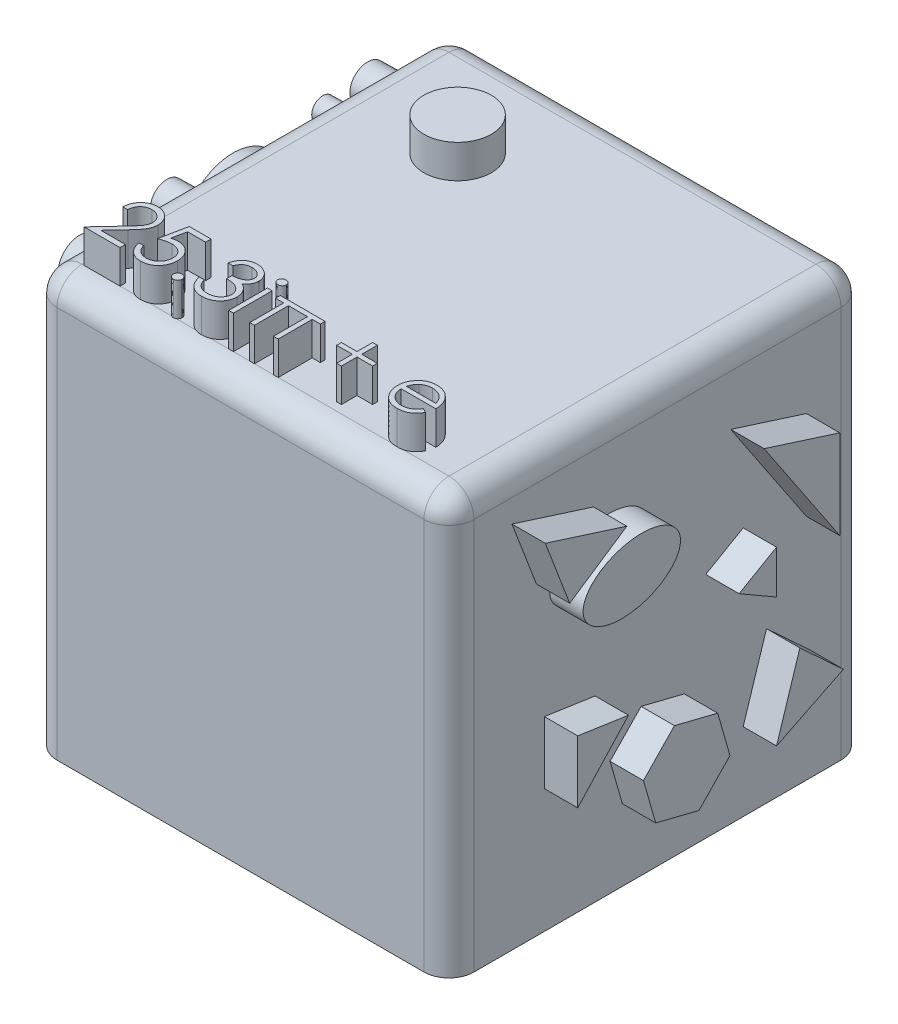
SolidWorks part; units mm, degrees
ref_plane "Front Plane" through (0, 0, 0) normal (0, 0, 1) x (1, 0, 0)
ref_plane "Top Plane" through (0, 0, 0) normal (0, 1, 0) x (1, 0, 0)
ref_plane "Right Plane" through (0, 0, 0) normal (1, 0, 0) x (0, 0, -1)
sketch "Sketch1" plane through (0, 0, 0) normal (0, 1, 0) x (1, 0, 0)
  line L1 (0, 0) -> (25, 0)
  line L2 (0, 0) -> (0, -25)
  line L3 (0, -25) -> (25, -25)
  line L4 (25, 0) -> (25, -25)
extrude "Boss-Extrude1" add sketch "Sketch1" along normal blind 25
fillet "Fillet1" radius 1.5 8 edges at (0, 12.5, 25) (0, 12.5, 0) (25, 12.5, 0) (25, 12.5, 25) (0, 25, 12.5) (12.5, 25, 0) (12.5, 25, 25) (25, 25, 12.5)
sketch "Sketch6" plane through (0, 25, 0) normal (0, 1, 0) x (1, 0, 0)
  circle A0 centre (6.997, -6.4811) radius 2.0261
  point P2 (0, 0)
extrude "Boss-Extrude5" add sketch "Sketch6" along normal blind 2
sketch "Sketch7" plane through (0, 0, 0) normal (0, -1, 0) x (-1, 0, 0)
  circle A0 centre (-5.9652, -19.1208) radius 3.5955
  circle A1 centre (-15.8104, -15.0795) radius 0.7155
  circle A2 centre (-16.5259, -19.5508) radius 2.0598
  circle A3 centre (-7.9428, -9.3616) radius 1.5861
  circle A4 centre (-17.1432, -9.7485) radius 2.3972
  circle A5 centre (-11.7691, -4.8903) radius 3.6277
extrude "Boss-Extrude6" add sketch "Sketch7" along normal blind 2
sketch "Sketch8" plane through (0, 0, 0) normal (-1, 0, 0) x (0, 0, 1)
  circle A0 centre (5.5679, 18.5843) radius 1.7646
  circle A1 centre (10.954, 19.6814) radius 3.1065
  circle A2 centre (7.8475, 13.647) radius 0.5476
  circle A3 centre (14.0605, 14.6943) radius 1.2507
  circle A4 centre (17.6367, 19.1329) radius 1.052
  circle A5 centre (10.1561, 9.6573) radius 0.4516
  circle A6 centre (3.8033, 11.0537) radius 1.6179
  circle A7 centre (7.3, 11.4028) radius 1.0224
  circle A8 centre (15.3112, 10.1089) radius 0.7751
  circle A9 centre (10.6077, 13.0995) radius 1.2373
  circle A10 centre (17.2378, 13.4436) radius 1.5191
  circle A11 centre (5.8671, 7.1638) radius 1.2175
  circle A12 centre (10.6077, 6.7149) radius 1.3695
  circle A13 centre (15.7416, 7.1638) radius 0.83
  circle A14 centre (3.8033, 2.8749) radius 1.88
  circle A15 centre (9.2381, 2.8749) radius 1.5372
  circle A16 centre (14.9116, 3.6728) radius 1.1514
  circle A17 centre (19.2326, 4.8242) radius 1.46
  circle A18 centre (19.7313, 10.1089) radius 1.7901
  circle A19 centre (20.1303, 16.9884) radius 1.3866
  circle A20 centre (20.1303, 21.776) radius 1.3419
  circle A21 centre (14.9116, 22.3745) radius 1.0233
  circle A22 centre (2.8749, 15.5421) radius 1.2468
  circle A23 centre (2.8749, 22.3745) radius 1.1046
  circle A24 centre (6.2661, 16.0907) radius 0.5576
  circle A25 centre (4.77, 14.2954) radius 0.2686
  circle A26 centre (9.2381, 16.0907) radius 0.6904
  circle A27 centre (2.3263, 7.862) radius 0.8879
  circle A28 centre (17.2378, 2.3263) radius 1.0673
  circle A29 centre (20.1303, 2.3263) radius 0.5985
  circle A30 centre (21.1277, 7.1638) radius 0.83
  circle A31 centre (12.3005, 10.6548) radius 1.3091
  circle A32 centre (5.5679, 22.3745) radius 0.6982
  circle A33 centre (2.3263, 19.1329) radius 0.7758
  circle A34 centre (21.1277, 13.4436) radius 0.8977
  circle A35 centre (15.7416, 16.9884) radius 0.9836
  circle A36 centre (14.9116, 19.9087) radius 0.4597
  circle A37 centre (13.2979, 7.1638) radius 0.8848
  circle A38 centre (12.3005, 1.9273) radius 0.8118
extrude "Boss-Extrude8" add sketch "Sketch8" along normal blind 2 draft 1
sketch "Sketch9" plane through (25, 0, 0) normal (1, 0, 0) x (0, 0, -1)
  line L1 (-10.1561, 5.5679) -> (-10.8912, 8.1379)
  line L2 (-10.8912, 8.1379) -> (-13.4845, 8.7863)
  line L3 (-13.4845, 8.7863) -> (-15.3427, 6.8646)
  line L4 (-15.3427, 6.8646) -> (-14.6075, 4.2945)
  line L5 (-14.6075, 4.2945) -> (-12.0142, 3.6462)
  line L6 (-12.0142, 3.6462) -> (-10.1561, 5.5679)
  circle A0 centre (-12.7494, 6.2162) radius 2.315 construction
  ellipse E0 centre (-16.0409, 17.8362) end of major axis (-18.9334, 17.1879) minor radius 1.8526
extrude "Boss-Extrude9" add sketch "Sketch9" along normal blind 2
sketch "Sketch10" plane through (25, 0, 0) normal (1, 0, 0) x (0, 0, -1)
  line L0 (-19.2825, 7.4131) -> (-19.2825, 11.1535)
  line L1 (-9.6075, 13.6969) -> (-7.3633, 12.4012)
  line L2 (-7.3633, 12.4012) -> (-7.3633, 14.9926)
  line L3 (-7.3633, 14.9926) -> (-9.6075, 13.6969)
  line L4 (-19.2825, 11.1535) -> (-16.2403, 10.7046)
  line L5 (-16.2403, 10.7046) -> (-19.2825, 7.4131)
  line L6 (-8.1113, 20.4794) -> (-3.5731, 19.0331)
  line L7 (-3.5731, 19.0331) -> (-3.5731, 13.6969)
  line L8 (-3.5731, 13.6969) -> (-8.1113, 20.4794)
  line L9 (-7.3633, 4.6702) -> (-5.9647, 9.0589)
  line L10 (-5.9647, 9.0589) -> (-3.3553, 6.6472)
  line L11 (-3.3553, 6.6472) -> (-7.3633, 4.6702)
  line L12 (-21.2275, 22.1251) -> (-16.3394, 20.5674)
  line L13 (-16.3394, 20.5674) -> (-19.7613, 18.2777)
  line L14 (-19.7613, 18.2777) -> (-21.2275, 22.1251)
  circle A0 centre (-8.1113, 13.6969) radius 0.7481 construction
extrude "Boss-Extrude10" add sketch "Sketch10" along normal blind 2
sketch "Sketch11" plane through (0, 25, 0) normal (0, 1, 0) x (1, 0, 0)
  text T0 "25.3iπ + e"
extrude "Boss-Extrude11" add sketch "Sketch11" along normal blind 2
